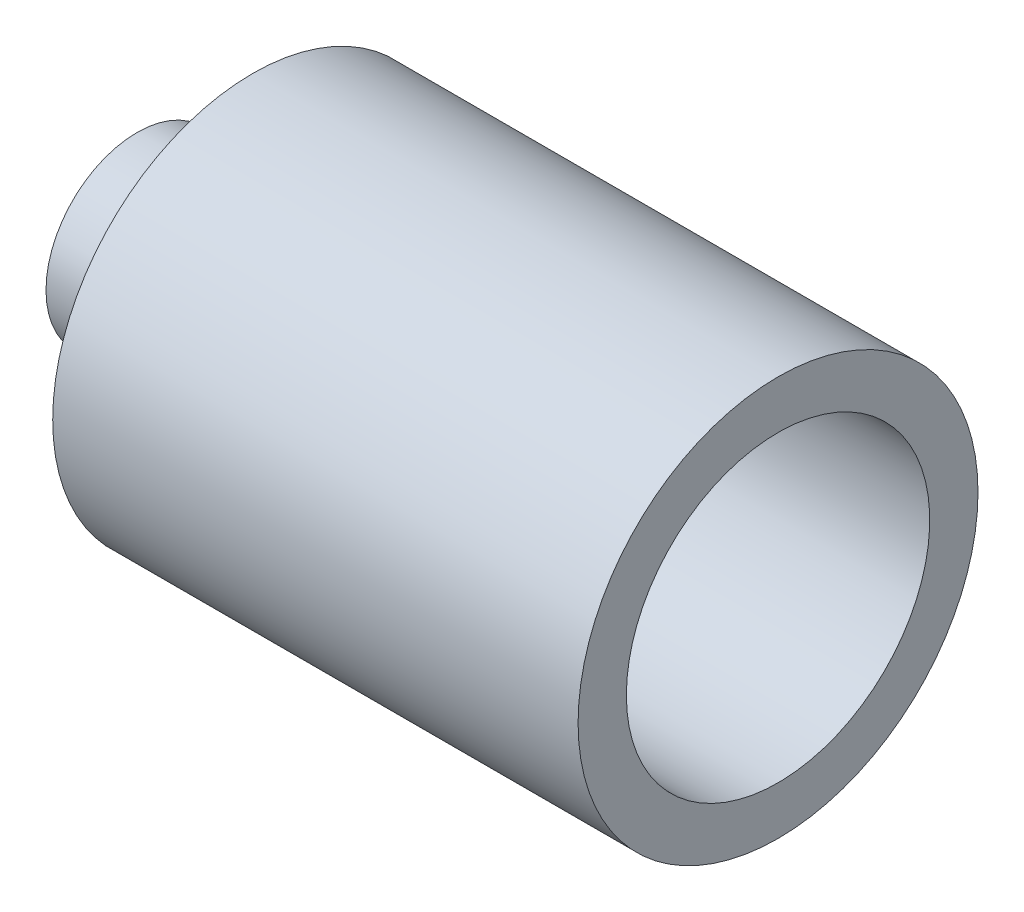
SolidWorks part; units mm, degrees
material "PET"
ref_plane "Front" through (0, 0, 0) normal (0, 0, 1) x (1, 0, 0)
ref_plane "Top" through (0, 0, 0) normal (0, 1, 0) x (1, 0, 0)
ref_plane "Right" through (0, 0, 0) normal (1, 0, 0) x (0, 0, -1)
ref_axis "Axis1" through (0, 0, 55) along (0, 0, -1)
sketch "Sketch1" plane through (0, 0, 0) normal (0, 0, 1) x (1, 0, 0)
  line L0 (0, 0) -> (38.1, 0) construction
  line L1 (38.1, 11) -> (38.1, 14.5)
  line L2 (38.1, 14.5) -> (0, 14.5)
  line L3 (0, 14.5) -> (0, 6.604)
  line L4 (0, 6.604) -> (-8.382, 6.604)
  line L5 (-8.382, 6.604) -> (-8.382, 3.429)
  line L6 (-8.382, 3.429) -> (5.08, 3.429)
  line L7 (38.1, 11) -> (5.08, 11)
  line L8 (5.08, 11) -> (5.08, 3.429)
  point P5 (-1.9923, 4.5423)
  point P13 (-10.1814, 1.1012)
  point P14 (0, 0)
  point P15 (0, 0)
  dimension "D1" = 38.1
  dimension "D2" = 22
  dimension "D3" = 29
  dimension "D4" = 13.208
  dimension "D5" = 3.175
  dimension "D6" = 8.382
  dimension "D7" = 33.02
revolve "Revolve1" add sketch "Sketch1" angle 360 about L0
